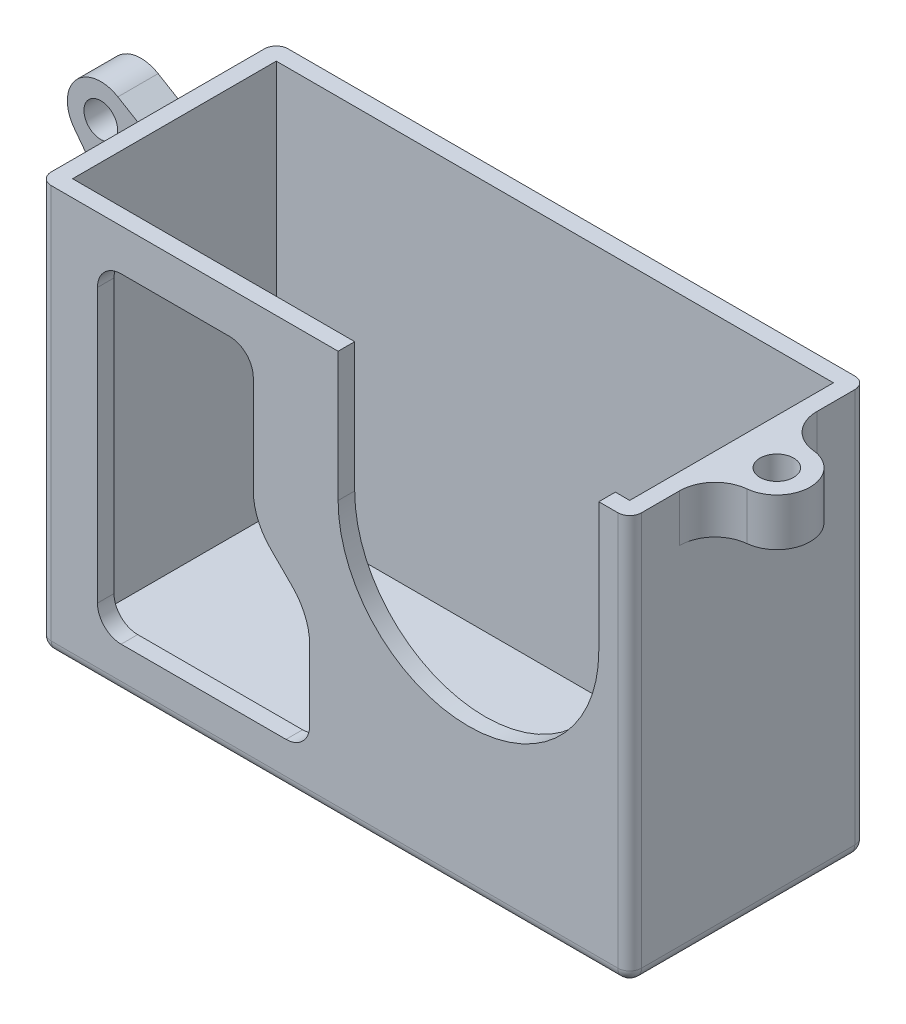
SolidWorks part; units mm, degrees
ref_plane "Front Plane" through (0, 0, 0) normal (0, 0, 1) x (1, 0, 0)
ref_plane "Top Plane" through (0, 0, 0) normal (0, 1, 0) x (1, 0, 0)
ref_plane "Right Plane" through (0, 0, 0) normal (1, 0, 0) x (0, 0, -1)
sketch "Sketch1" plane through (0, 0, 0) normal (0, 0, 1) x (1, 0, 0)
  line L1 (0, 0) -> (59.7408, 0)
  line L2 (0, 0) -> (0, 41.783)
  line L4 (59.7408, 0) -> (59.7408, 41.783)
  dimension "D1" = 59.7408
  dimension "D2" = 41.783
ref_plane "Plane1" through (0, 41.783, 0) normal (0, 1, 0) x (1, 0, 0)
sketch "Sketch3" plane through (0, 41.783, 0) normal (0, 1, 0) x (1, 0, 0)
  line L1 (-1.778, 10.922) -> (0, 10.922)
  line L2 (-1.778, 10.922) -> (-1.778, -10.922)
  line L3 (-1.778, -10.922) -> (0, -10.922)
  line L4 (0, 10.922) -> (0, -10.922)
  point P4 (-1.778, 0)
  dimension "D1" = 21.844
  dimension "D2" = 1.778
sweep "Sweep1" add profiles "Sketch3" path "Sketch1"
sketch "Sketch4" plane through (0, 0, -10.922) normal (0, 0, -1) x (-1, 0, 0)
  line L1 (-61.5188, 41.783) -> (1.778, 41.783)
  line L2 (-61.5188, 41.783) -> (-61.5188, -1.778)
  line L3 (-61.5188, -1.778) -> (1.778, -1.778)
  line L4 (1.778, 41.783) -> (1.778, -1.778)
extrude "Boss-Extrude1" add sketch "Sketch4" along normal blind 1.778
sketch "Sketch5" plane through (0, 0, 10.922) normal (0, 0, 1) x (1, 0, 0)
  line L0 (0, 0) -> (0, 41.783) construction
  line L1 (0.381, 41.402) -> (59.3598, 41.402) construction
  line L2 (0.381, 41.402) -> (0.381, 0.381) construction
  line L3 (0.381, 0.381) -> (59.3598, 0.381) construction
  line L4 (59.3598, 41.402) -> (59.3598, 0.381) construction
  line L5 (5.715, 36.068) -> (19.8882, 36.068) construction
  line L6 (5.715, 36.068) -> (5.715, 18.8468) construction
  line L7 (5.715, 18.8468) -> (19.8882, 18.8468) construction
  line L8 (19.8882, 36.068) -> (19.8882, 18.8468) construction
  line L9 (59.7408, 0) -> (0, 0) construction
  line L10 (59.7408, 41.783) -> (59.7408, 0) construction
  line L11 (61.5188, 41.783) -> (59.7408, 41.783) construction
  line L13 (-1.778, 41.783) -> (61.5188, 41.783)
  line L14 (-1.778, 41.783) -> (-1.778, -1.778)
  line L15 (-1.778, -1.778) -> (61.5188, -1.778)
  line L16 (61.5188, 41.783) -> (61.5188, -1.778)
  line L18 (4.445, 34.798) -> (4.445, 5.4864)
  line L19 (6.985, 2.9464) -> (24.6634, 2.9464)
  line L20 (27.2034, 5.4864) -> (27.2034, 12.9906)
  line L21 (25.3435, 17.4808) -> (23.0181, 19.8062)
  line L22 (21.1582, 24.2964) -> (21.1582, 34.798)
  line L23 (12.8016, 10.4013) -> (12.8016, 4.2164) construction
  line L24 (23.2791, 6.8072) -> (25.9334, 6.8072) construction
  line L25 (23.2791, 13.9954) -> (26.054, 16.7703) construction
  line L26 (23.2791, 13.9954) -> (25.9334, 13.9954) construction
  line L27 (18.6182, 37.338) -> (6.985, 37.338)
  line L29 (30.2514, 27.9197) -> (30.2514, 41.783)
  line L30 (30.2514, 41.783) -> (58.2016, 41.783)
  line L31 (58.2016, 41.783) -> (58.2016, 27.9197)
  circle A0 centre (44.2265, 27.9197) radius 11.4351 construction
  circle A1 centre (12.8016, 10.4013) radius 6.1849 construction
  circle A2 centre (23.2791, 13.9954) radius 2.6543 construction
  circle A3 centre (23.2791, 6.8072) radius 2.6543 construction
  arc A7 (24.6634, 2.9464) -> (27.2034, 5.4864) centre (24.6634, 5.4864) ccw
  arc A8 (21.1582, 34.798) -> (18.6182, 37.338) centre (18.6182, 34.798) ccw
  arc A9 (4.445, 34.798) -> (6.985, 37.338) centre (6.985, 34.798) cw
  arc A10 (4.445, 5.4864) -> (6.985, 2.9464) centre (6.985, 5.4864) ccw
  arc A11 (23.0181, 19.8062) -> (21.1582, 24.2964) centre (27.5082, 24.2964) cw
  arc A12 (27.2034, 12.9906) -> (25.3435, 17.4808) centre (20.8534, 12.9906) ccw
  arc A13 (30.2514, 27.9197) -> (58.2016, 27.9197) centre (44.2265, 27.9197) ccw
  circle A14 centre (44.2265, 27.9197) radius 13.9751 construction
  point P44 (25.156, 15.8723)
  line M10 (59.7408, 41.783) -> (59.7408, 0)
  line M11 (59.7408, 0) -> (0, 0)
  line M12 (0, 0) -> (0, 41.783)
  line M13 (0, 41.783) -> (-1.778, 41.783)
  line M14 (-1.778, 41.783) -> (-1.778, -1.778)
  line M15 (-1.778, -1.778) -> (61.5188, -1.778)
  line M16 (61.5188, -1.778) -> (61.5188, 41.783)
  line M17 (61.5188, 41.783) -> (59.7408, 41.783)
  dimension "D1" = 22.8702
  dimension "D12" = 7.1882
  dimension "D13" = 6.4262
  dimension "D14" = 12.3698
  dimension "D15" = 10.0203
  dimension "D16" = 12.4206
  dimension "D18" = 5.3086
  dimension "D27" = 2.54
  dimension "D28" = 6.35
  dimension "D19" = 2.54
  dimension "D2" = 15.1333
  dimension "D3" = 13.4823
  dimension "D4" = 5.334
  dimension "D5" = 0.381
  dimension "D6" = 0.381
  dimension "D7" = 0.381
  dimension "D8" = 0.381
  dimension "D9" = 17.2212
  dimension "D10" = 5.334
  dimension "D11" = 14.1732
  dimension "D17" = 10.4775
  dimension "D20" = 1.27
  dimension "D21" = 1.27
  dimension "D22" = 1.27
  dimension "D23" = 1.27
  dimension "D24" = 45
  dimension "D25" = 1.27
  dimension "D26" = 1.27
extrude "Boss-Extrude2" add sketch "Sketch5" along normal blind 1.778 contours A13 L29 L13 L31 A12 L20 A7 L19 A10 L18 A9 L27 A8 L22 A11 L21 M12 M11 M10 | M17 M10 M11 M12 M13 M14 M15 M16
sketch "Sketch6" plane through (0, 41.783, 0) normal (0, 1, 0) x (1, 0, 0)
  line L0 (61.5188, 12.7) -> (61.5188, -12.7) construction
  line L1 (64.5922, 0) -> (62.7888, 0) construction
  line L2 (64.5922, 3.5814) -> (61.5188, 3.5814)
  line L3 (61.5188, 3.5814) -> (61.5188, -3.5814)
  line L4 (61.5188, -3.5814) -> (64.5922, -3.5814)
  circle A0 centre (64.5922, 0) radius 1.8034
  arc A1 (64.5922, -3.5814) -> (64.5922, 3.5814) centre (64.5922, 0) ccw
  circle A2 centre (64.5922, 0) radius 3.5814 construction
  point P7 (61.5188, 0)
  dimension "D2" = 3.6068
  dimension "D3" = 1.27
  dimension "D1" = 1.778
extrude "Boss-Extrude3" add sketch "Sketch6" against normal blind 5.08
fillet "Fillet2" radius 3.81 2 edges at (61.5188, 39.243, -3.5814) (61.5188, 39.243, 3.5814)
sketch "Sketch7" plane through (0, 0, 12.7) normal (0, 0, 1) x (1, 0, 0)
  line L0 (-1.778, 41.783) -> (30.2514, 41.783) construction
  line L1 (-1.778, 41.783) -> (-1.778, -1.778) construction
  line L2 (-1.778, 41.783) -> (-3.9023, 43.0533)
  line L3 (-5.7404, 36.3982) -> (-1.778, 36.3982) construction
  line L4 (-1.778, 36.3982) -> (-1.778, 41.783)
  line L5 (-8.5997, 37.8231) -> (-1.778, 28.7782)
  circle A0 centre (-5.7404, 39.9796) radius 1.8034
  arc A1 (-3.9023, 43.0533) -> (-8.5997, 37.8231) centre (-5.7404, 39.9796) ccw
  circle A2 centre (-5.7404, 39.9796) radius 3.5814 construction
  arc A3 (-8.5997, 37.8231) -> (-5.7404, 36.3982) centre (-5.7404, 39.9796) ccw construction
  line M4 (-1.778, 41.783) -> (-1.778, -1.778)
  dimension "D2" = 3.6068
  dimension "D3" = 1.8034
  dimension "D4" = 3.9624
  dimension "D5" = 7.62
  dimension "D1" = 1.778
extrude "Boss-Extrude4" add sketch "Sketch7" against normal up to surface (25.4 mm away) contours L2 A1 L5 A0 M4 up to face at (29.8704, 20.0025, -12.7)
sketch "Sketch8" plane through (0, 41.783, 0) normal (0, 1, 0) x (1, 0, 0)
  line L0 (-1.778, 12.7) -> (-1.778, -12.7) construction
  line L1 (-1.778, -2.159) -> (-9.3218, -2.159)
  line L2 (-1.778, -2.159) -> (-1.778, 2.159)
  line L3 (-1.778, 2.159) -> (-9.3218, 2.159)
  line L4 (-9.3218, -2.159) -> (-9.3218, 2.159)
  line L5 (-9.3218, 12.7) -> (-9.3218, -12.7) construction
  line L7 (-9.3218, 12.7) -> (-1.778, 12.7)
  line L8 (-9.3218, 12.7) -> (-9.3218, -12.7)
  line L9 (-9.3218, -12.7) -> (-1.778, -12.7)
  line L10 (-1.778, 12.7) -> (-1.778, -12.7)
  point P8 (-1.778, 0)
  line M8 (-1.778, 12.7) -> (-1.778, -12.7)
  dimension "D1" = 4.318
extrude "Cut-Extrude1" cut sketch "Sketch8" against normal through all both and the other way through all contours L7 L8 L3 M8 | L8 L9 L1 M8
sketch "Sketch13" plane through (-1.778, 0, 0) normal (-1, 0, 0) x (0, 0, 1)
  line L0 (-21.082, -1.778) -> (-12.7, -1.778)
  line L1 (-21.082, 5.842) -> (-13.462, 5.842) construction
  line L2 (-12.7, -1.778) -> (-12.7, 41.783) construction
  line L3 (-21.082, 13.462) -> (-12.7, 13.462)
  line L4 (-12.7, 13.462) -> (-12.7, -1.778)
  circle A0 centre (-21.082, 5.842) radius 2.5248
  arc A1 (-21.082, 13.462) -> (-21.082, -1.778) centre (-21.082, 5.842) ccw
  arc A2 (-21.082, -1.778) -> (-21.082, 13.462) centre (-21.082, 5.842) ccw construction
  dimension "D1" = 5.0495
  dimension "D2" = 15.24
  dimension "D3" = 0.762
extrude "Boss-Extrude5" add sketch "Sketch13" against normal up to surface (63.2968 mm away) up to face at (61.5188, 29.6227, 0)
sketch "Sketch14" plane through (0, 13.462, 0) normal (0, 1, 0) x (1, 0, 0)
  line L0 (61.5188, 12.7) -> (-1.778, 12.7) construction
  line L1 (25.6248, 12.7) -> (28.1419, 12.7)
  line L2 (25.6248, 12.7) -> (25.6248, 28.702)
  line L3 (25.6248, 28.702) -> (28.1419, 28.702)
  line L4 (28.1419, 12.7) -> (28.1419, 28.702)
  line L5 (61.5188, 28.702) -> (-1.778, 28.702) construction
  line L6 (28.1419, 28.702) -> (31.5989, 28.702) construction
  line L7 (31.5989, 28.702) -> (34.116, 28.702)
  line L8 (31.5989, 28.702) -> (31.5989, 12.7)
  line L9 (31.5989, 12.7) -> (34.116, 12.7)
  line L10 (34.116, 28.702) -> (34.116, 12.7)
  line L12 (-1.778, 28.702) -> (61.5188, 28.702)
  line L13 (-1.778, 28.702) -> (-1.778, 12.7)
  line L14 (-1.778, 12.7) -> (61.5188, 12.7)
  line L15 (61.5188, 28.702) -> (61.5188, 12.7)
  point P12 (29.8704, 28.702)
  point P13 (29.8704, 12.7)
  line M7 (-1.778, 12.7) -> (61.5188, 12.7)
  line M8 (61.5188, 12.7) -> (61.5188, 21.082)
  line M9 (61.5188, 21.082) -> (-1.778, 21.082)
  line M10 (-1.778, 21.082) -> (-1.778, 12.7)
  dimension "D1" = 2.5171
  dimension "D2" = 3.4569
extrude "Cut-Extrude2" cut sketch "Sketch14" against normal through all contours L12 L13 L2 M9 | L2 M7 M9 M10 | L10 M9 M7 M8 | L15 L12 L10 M9 | L12 L4 L8 M9 | L8 L4 M9 M7
fillet "Fillet3" radius 8.382 2 edges at (26.8834, 13.462, -12.7) (32.8574, 13.462, -12.7)
fillet "Fillet4" radius 1.27 10 edges at (61.5188, -1.778, 0) (-1.778, 20.0025, 12.7) (-1.778, -1.778, 0) (-1.778, 20.0025, -12.7) (11.9234, -1.778, -12.7) (47.8174, -1.778, -12.7) (29.8704, -1.778, -12.7) (61.5188, 20.0025, -12.7) (29.8704, -1.778, 12.7) (61.5188, 20.0025, 12.7)
